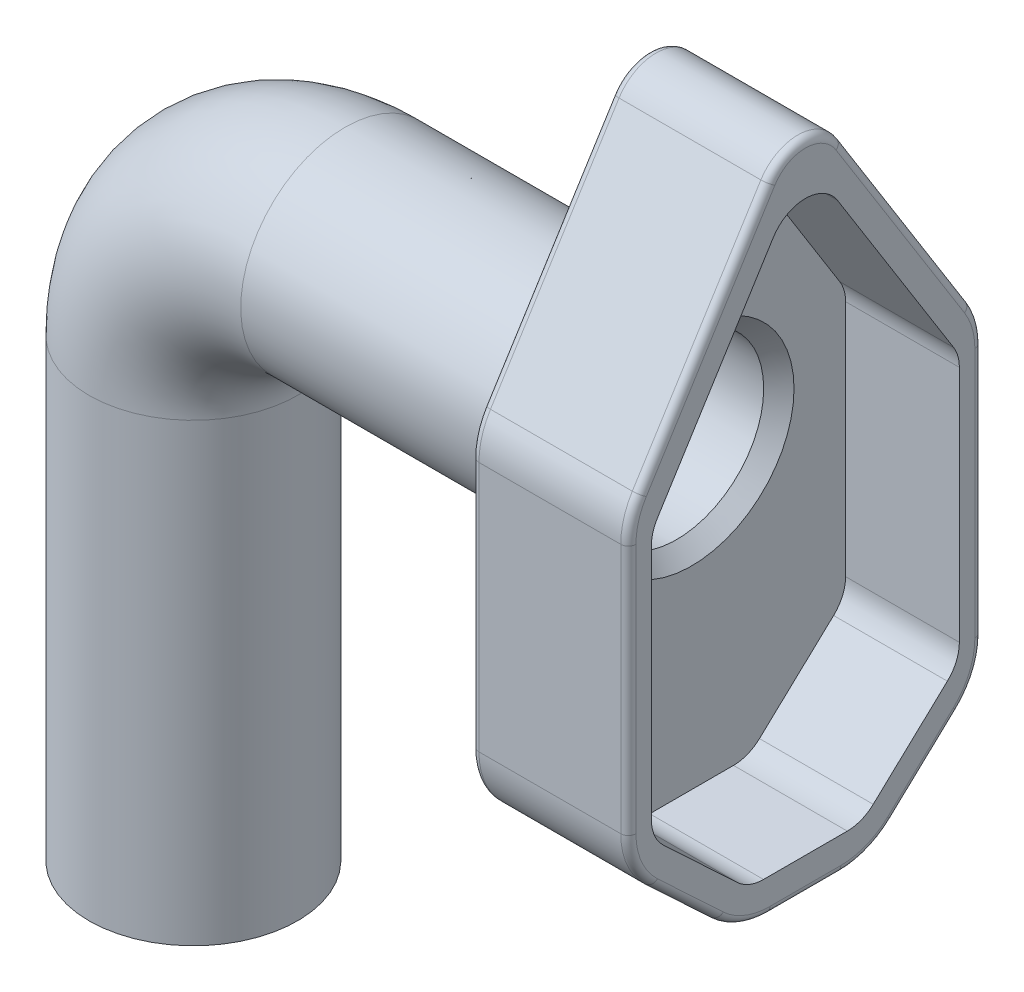
SolidWorks part; units mm, degrees
ref_plane "Front Plane" through (0, 0, 0) normal (1, 0, 0) x (0, 1, 0)
ref_plane "Top Plane" through (0, 0, 0) normal (0, 0, 1) x (0, 1, 0)
ref_plane "Right Plane" through (0, 0, 0) normal (0, 1, 0) x (-1, 0, 0)
sketch "Sketch1" plane through (0, 0, 0) normal (1, 0, 0) x (0, 1, 0)
  line L0 (0, 0) -> (25.6534, -16.0621)
  line L1 (0, 0) -> (-35, 0)
  line L2 (0, 0) -> (0, -40.6)
  line L3 (0, -40.6) -> (-35, -40.6)
  line L4 (-35, 0) -> (-35, -40.6)
  line L5 (25.6534, -24.5379) -> (0, -40.6)
  line L6 (-35, 0) -> (-47, -12.8)
  line L7 (-47, -12.8) -> (-47, -27.8)
  line L8 (-47, -27.8) -> (-35, -40.6)
  arc A0 (25.6534, -24.5379) -> (25.6534, -16.0621) centre (23, -20.3) ccw
  point P5 (-47, -20.3)
  point P7 (0, -20.3)
  point P10 (32.4218, -20.3)
  point P13 (-35, -20.3)
  point P14 (28, -20.3)
  dimension "D2" = 5
  dimension "D6" = 28
  dimension "D1" = 40.6
  dimension "D3" = 15
  dimension "D4" = 75
  dimension "D5" = 35
extrude "Boss-Extrude1" add sketch "Sketch1" along normal blind 18 contours L1 L4 L3 L2 | L7 L8 L4 L6 | L5 A0 L0 L2 region at (0, -17.5, -20.3) region at (0, 10.3898, -20.3) region at (0, -40.0791, -20.3)
scale "Scale1" scale about centroid uniform scaling yes scale factor 1.15
sketch "Sketch7" plane through (19.35, 0, 0) normal (1, 0, 0) x (0, 1, 0)
  line L0 (-0.5765, 0) -> (25.0769, -16.0621)
  line L1 (-0.5765, 0) -> (-35.5765, 0)
  line L2 (-0.5765, 0) -> (-0.5765, -40.6)
  line L3 (-0.5765, -40.6) -> (-35.5765, -40.6)
  line L4 (-35.5765, 0) -> (-35.5765, -40.6)
  line L5 (25.0769, -24.5379) -> (-0.5765, -40.6)
  line L6 (-35.5765, 0) -> (-47.5765, -12.8)
  line L7 (-47.5765, -12.8) -> (-47.5765, -27.8)
  line L8 (-47.5765, -27.8) -> (-35.5765, -40.6)
  line L9 (1.9735, 3.045) -> (-38.2765, 3.045) construction
  line L10 (-52.0765, -11.675) -> (-52.0765, -28.925) construction
  arc A0 (25.0769, -24.5379) -> (25.0769, -16.0621) centre (22.4235, -20.3) ccw
  arc A1 (31.475, -25.1735) -> (31.475, -15.4265) centre (28.4235, -20.3) ccw construction
  point P4 (-47.5765, -20.3)
  point P6 (-0.5765, -20.3)
  point P11 (-35.5765, -20.3)
  point P12 (27.4235, -20.3)
  point P17 (-52.0765, -20.3)
  point P21 (34.1735, -20.3)
  dimension "D2" = 5
  dimension "D1" = 40.6
  dimension "D3" = 15
  dimension "D4" = 75
  dimension "D5" = 35
  dimension "D6" = 28
  dimension "D7" = 4.5
extrude "Cut-Extrude1" cut sketch "Sketch7" against normal blind 15 contours L1 L4 L3 L2 | L7 L8 L4 L6 | L5 A0 L0 L2 region at (19.35, -18.0765, -20.3) region at (19.35, 9.8134, -20.3) region at (19.35, -40.6556, -20.3)
fillet "Fillet1" radius 10 6 edges at (9, 1.9735, 3.045) (9, -38.2765, 3.045) (9, -52.0765, -11.675) (9, -52.0765, -28.925) (9, 1.9735, -43.645) (9, -38.2765, -43.645)
fillet "Fillet2" radius 5 6 edges at (11.85, -0.5765, -40.6) (11.85, -35.5765, -40.6) (11.85, -47.5765, -27.8) (11.85, -47.5765, -12.8) (11.85, -0.5765, 0) (11.85, -35.5765, 0)
fillet "Fillet3" radius 1 14 edges at (19.35, -45.3057, -36.1472) (19.35, -51.3758, -28.6479) (19.35, -52.0765, -20.3) (19.35, -51.3758, -11.9521) (19.35, -45.3057, -4.4528) (19.35, -37.9194, 2.2209) (19.35, -17.4215, 3.045) (19.35, 1.8619, 2.6564) (19.35, 17.9415, -6.9529) (19.35, 34.1735, -20.3) (19.35, 17.9415, -33.6471) (19.35, 1.8619, -43.2564) (19.35, -17.4215, -43.645) (19.35, -37.9194, -42.8209)
fillet "Fillet4" radius 1 14 edges at (-1.35, 1.8619, -43.2564) (-1.35, 17.9415, -33.6471) (-1.35, 34.1735, -20.3) (-1.35, 17.9415, -6.9529) (-1.35, 1.8619, 2.6564) (-1.35, -17.4215, 3.045) (-1.35, -37.9194, 2.2209) (-1.35, -45.3057, -4.4528) (-1.35, -51.3758, -11.9521) (-1.35, -52.0765, -20.3) (-1.35, -51.3758, -28.6479) (-1.35, -45.3057, -36.1472) (-1.35, -37.9194, -42.8209) (-1.35, -17.4215, -43.645)
sketch "Sketch9" plane through (-1.35, 0, 0) normal (-1, 0, 0) x (0, -1, 0)
  line L0 (0.8988, 2.045) -> (0.8988, -43.645) construction
  line L1 (51.0765, -24.9705) -> (51.0765, -15.6295) construction
  circle A0 centre (8.5434, -20.3) radius 11.5
  point P8 (51.0765, -20.3)
  point P9 (0, 0)
  dimension "D1" = 23
extrude "Cut-Extrude2" cut sketch "Sketch9" against normal through all
chamfer "Chamfer1" distance 2 angle 45 1 edges at (4.35, -8.5434, -31.8)
sketch "Sketch10" plane through (0, -52.0765, 0) normal (0, -1, 0) x (1, 0, 0)
  line L0 (-1.35, -20.3) -> (19.35, -20.3) construction
  line L1 (-1.35, -8.8) -> (-1.35, -31.8) construction
  line L2 (19.35, -15.6295) -> (19.35, -24.9705) construction
ref_plane "Plane1" through (0, 0, -20.3) normal (0, 0, 1) x (1, 0, 0)
sketch "Sketch11" plane through (0, 0, -20.3) normal (0, 0, 1) x (1, 0, 0)
  line L0 (-1.35, -8.5434) -> (-41.35, -8.5434)
  line L1 (-61.35, -28.5434) -> (-61.35, -88.5434)
  arc A0 (-41.35, -8.5434) -> (-61.35, -28.5434) centre (-41.35, -28.5434) ccw
  dimension "D1" = 20
  dimension "D2" = 40
  dimension "D3" = 60
sweep "Sweep1" add path "Sketch11" circular profile diameter 27.5 parameters "D3"=27.5
sweep "Cut-Sweep2" cut path "Sketch11<3>" circular profile diameter 23 parameters "D3"=23
sketch "Sketch11<3>" plane through (0, 0, -20.3) normal (0, 0, 1) x (1, 0, 0) same geometry as "Sketch11"
sketch "Sketch13" plane through (0, -88.5434, 0) normal (0, -1, 0) x (1, 0, 0)
  line L0 (-61.35, -20.3) -> (-61.35, -52.718) construction
  line L1 (-63.5647, -27.4049) -> (-59.1353, -27.4049)
  line L2 (-63.5647, -27.4049) -> (-63.5647, -32.8925)
  line L3 (-63.5647, -32.8925) -> (-59.1353, -32.8925)
  line L4 (-59.1353, -27.4049) -> (-59.1353, -32.8925)
  point P8 (-61.35, -27.4049)
extrude "Cut-Extrude3" cut sketch "Sketch13" against normal blind 10
sketch "Sketch34" plane through (-63.5647, 0, 0) normal (1, 0, 0) x (0, 1, 0)
  line L1 (-78.5776, -30.9554) -> (-81.3837, -30.9554)
  line L2 (-78.5776, -30.9554) -> (-78.5776, -33.0191)
  line L3 (-78.5776, -33.0191) -> (-81.3837, -33.0191)
  line L4 (-81.3837, -30.9554) -> (-81.3837, -33.0191)
extrude "Cut-Extrude6" cut sketch "Sketch34" against normal blind 2
